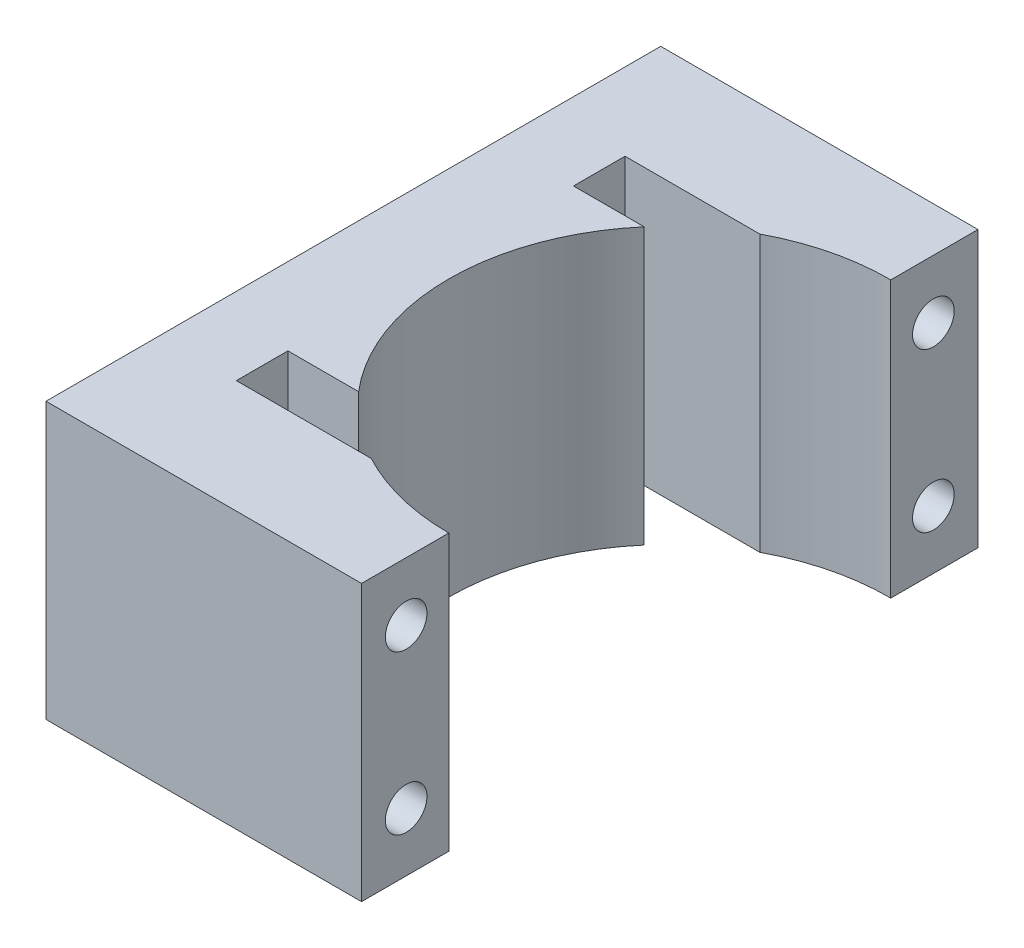
SolidWorks part; units mm, degrees
ref_plane "前视基准面" through (0, 0, 0) normal (0, 0, 1) x (1, 0, 0)
ref_plane "上视基准面" through (0, 0, 0) normal (0, 1, 0) x (1, 0, 0)
ref_plane "右视基准面" through (0, 0, 0) normal (1, 0, 0) x (0, 0, -1)
other "Configuration Table"
sketch "草图1" plane through (0, 0, 0) normal (0, 1, 0) x (1, 0, 0)
  line L0 (0, 15.5) -> (31.825, 15.5) construction
  line L1 (0, 0) -> (15.9125, 0)
  line L2 (0, 0) -> (0, 31)
  line L3 (0, 31) -> (16, 31)
  line L5 (16, 26.5997) -> (16, 31)
  line L6 (15.9125, 4.4) -> (15.9125, 0)
  line L7 (3.9, 5.7) -> (3.9, 8.3)
  line L8 (3.9, 25.3) -> (10.7, 25.3)
  line L9 (3.9, 5.7) -> (10.7, 5.7)
  line L10 (3.9, 22.7) -> (7.4644, 22.7)
  line L11 (3.9, 8.3) -> (7.4644, 8.3)
  line L12 (3.9, 22.7) -> (3.9, 25.3)
  arc A4 (16, 26.5997) -> (10.7, 25.3) centre (15.9125, 15.5) ccw
  arc A5 (7.4644, 22.7) -> (7.4644, 8.3) centre (15.9125, 15.5) ccw
  arc A6 (10.7, 5.7) -> (15.9125, 4.4) centre (15.9125, 15.5) ccw
  point P1 (16, 28.7998)
  point P14 (0, 0)
  dimension "D1" = 19.6
  dimension "D5" = 11.1
  dimension "D6" = 5.3
  dimension "D2" = 16
  dimension "D3" = 31
  dimension "D4" = 12.1
  dimension "D7" = 4.4
  dimension "D8" = 2.6
  dimension "D9" = 2.6
extrude "凸台-拉伸1" add sketch "草图1" along normal blind 13.9
sketch "草图2" plane through (0, 0, 0) normal (-1, 0, 0) x (0, 0, 1)
  line L0 (-28.75, 10.95) -> (-2.25, 10.95) construction
  line L1 (-28.75, 10.95) -> (-28.75, 2.95) construction
  line L2 (-15.5, 13.9) -> (-15.5, 0) construction
  line L3 (-31, 13.9) -> (0, 13.9) construction
  line L4 (-31, 0) -> (0, 0) construction
  line L5 (-31, 6.95) -> (0, 6.95) construction
  line L6 (-31, 13.9) -> (-31, 0) construction
  line L7 (0, 13.9) -> (0, 0) construction
  circle A0 centre (-28.75, 10.95) radius 1.05
  circle A1 centre (-2.25, 10.95) radius 1.05
  circle A2 centre (-2.25, 2.95) radius 1.05
  circle A3 centre (-28.75, 2.95) radius 1.05
  dimension "D1" = 2.1
  dimension "D3" = 26.5
  dimension "D4" = 8
  dimension "D6" = 4
  dimension "D7" = 13.25
  dimension "D8" = 90
  dimension "D2" = 2
  dimension "D5" = 2
extrude "切除-拉伸1" cut sketch "草图2" against normal through all contours A0 | A3 | A1 | A2
